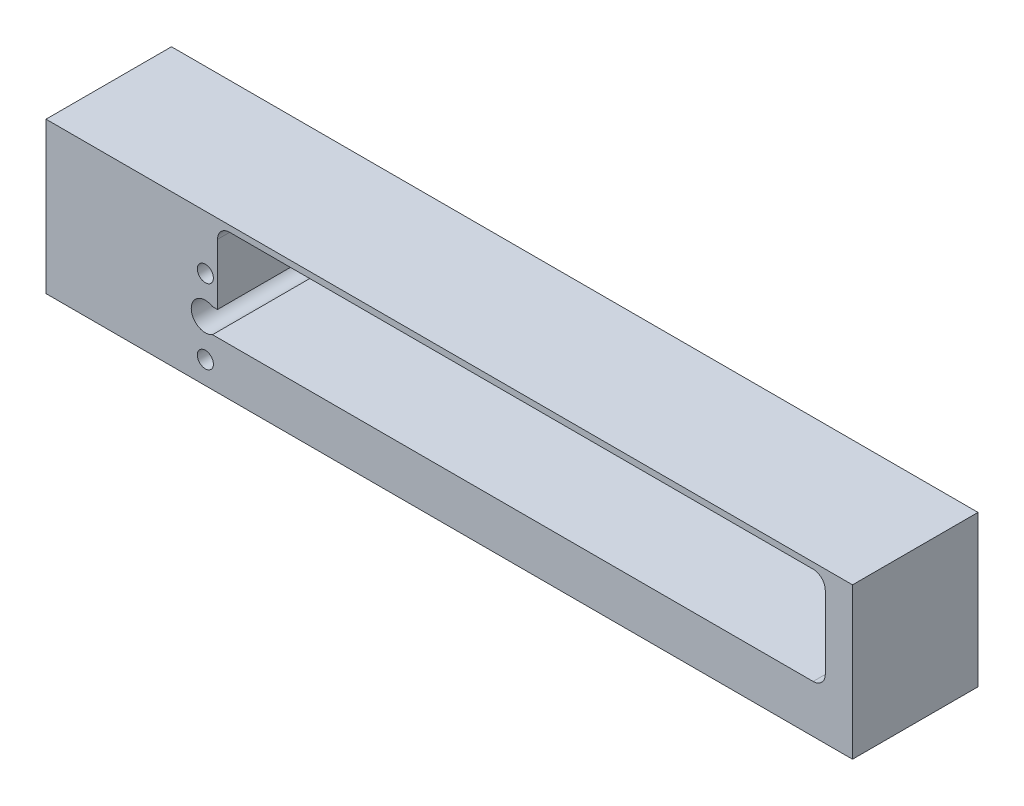
SolidWorks part; units mm, degrees
ref_plane "Front Plane" through (0, 0, 0) normal (0, 0, 1) x (1, 0, 0)
ref_plane "Top Plane" through (0, 0, 0) normal (0, 1, 0) x (1, 0, 0)
ref_plane "Right Plane" through (0, 0, 0) normal (1, 0, 0) x (0, 0, -1)
sketch "Sketch1" plane through (0, 0, 0) normal (0, 0, 1) x (1, 0, 0)
  line L0 (0, 0) -> (0, 152.64) construction
  line L1 (-406.4, -152.64) -> (406.4, -152.64)
  line L2 (-406.4, -152.64) -> (-406.4, 152.64)
  line L5 (-406.4, -152.64) -> (406.4, 152.64) construction
  line L6 (-406.4, 152.64) -> (406.4, -152.64) construction
  line L7 (0, 152.64) -> (0, 95.04)
  line L8 (0, 0) -> (406.4, 0) construction
  line L9 (-406.4, 152.64) -> (-406.4, 232.64)
  line L10 (-406.4, 232.64) -> (1650.5081, 232.64)
  line L11 (406.4, -152.64) -> (1650.5081, -152.64)
  line L12 (1650.5081, -152.64) -> (1650.5081, 232.64)
  circle A0 centre (0, 0) radius 36
  circle A1 centre (0, 95.04) radius 20.52
  circle A2 centre (0, -95.04) radius 20.52
  point P0 (0, 0)
extrude "Boss-Extrude1" add sketch "Sketch1" along normal blind 320 contours A1 L2 L1 A0 A2 region at (627.3717, 40.3419, 0)
sketch "Sketch2" plane through (0, 0, 320) normal (0, 0, 1) x (1, 0, 0)
  line L0 (258.5862, -31) -> (258.5862, 217) construction
  line L14 (31, 0) -> (62, 0) construction
  line L15 (1581, 186) -> (1550, 186) construction
  line L16 (1581, 0) -> (1581, 186)
  line L17 (31, 0) -> (62, 0) construction
  line L18 (1519, 0) -> (1550, 0) construction
  line L19 (62, 217) -> (1550, 217)
  line L20 (18.303, -31) -> (1550, -31)
  line L21 (31, 186) -> (31, 53.4696)
  line L22 (18.303, 31) -> (31, 31)
  line L23 (31, 31) -> (31, 53.4696)
  arc A2 (1550, -31) -> (1581, 0) centre (1550, 0) ccw
  arc A3 (1581, 186) -> (1550, 217) centre (1550, 186) ccw
  arc A4 (62, 217) -> (31, 186) centre (62, 186) ccw
  arc A5 (18.303, -31) -> (18.303, 31) centre (0, 0) ccw
  circle M2 centre (0, 0) radius 36
extrude "Cut-Extrude1" cut sketch "Sketch2" against normal blind 310 contours L19 A4 L21 L23 L22 L20 A2 L16 A3 M2 region at (805.5649, 92.9346, 320)
